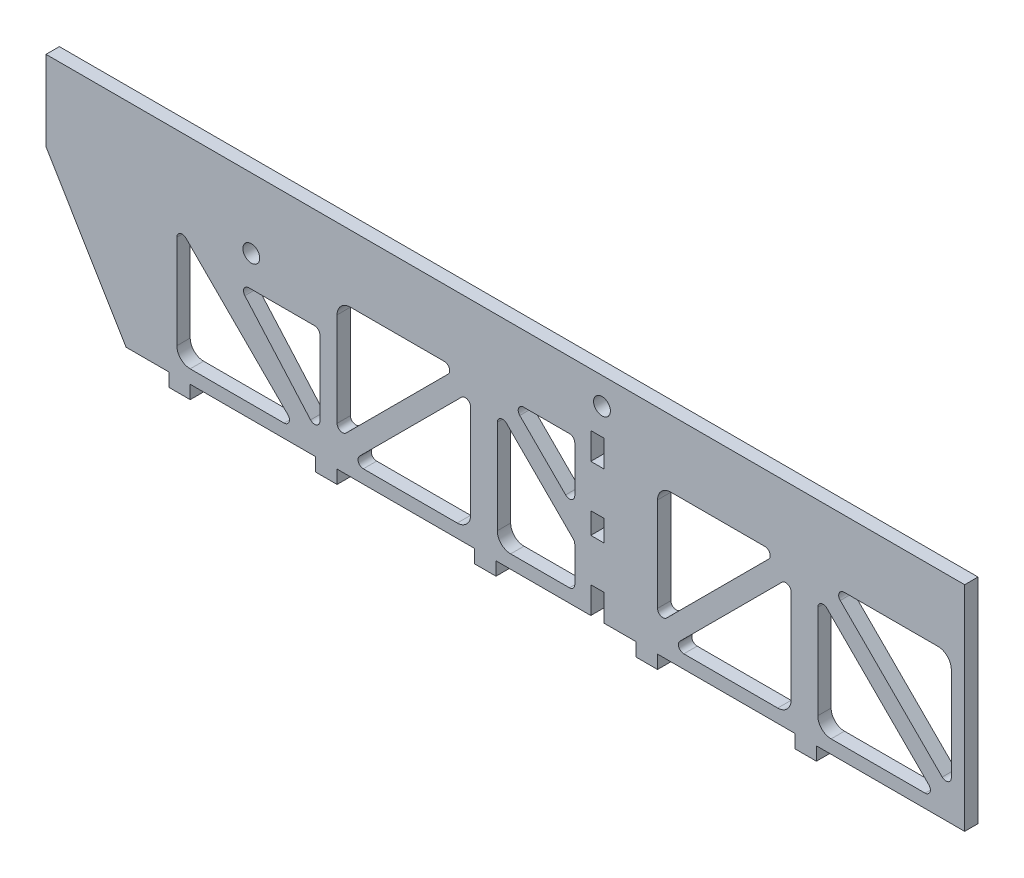
SolidWorks part; units mm, degrees
material "Pine"
ref_plane "Front Plane" through (0, 0, 0) normal (0, 0, 1) x (1, 0, 0)
ref_plane "Top Plane" through (0, 0, 0) normal (0, 1, 0) x (1, 0, 0)
ref_plane "Right Plane" through (0, 0, 0) normal (1, 0, 0) x (0, 0, -1)
sketch "Model" plane through (0, 0, 0) normal (0, 0, 1) x (1, 0, 0)
  line L0 (-306.6281, 15.625) -> (-306.6281, 51.1493)
  line L1 (-309.1681, 53.6893) -> (-340.406, 53.6893)
  line L2 (-342.3135, 49.472) -> (-311.0755, 13.9477)
  line L8 (-171.2321, 6.35) -> (-215.9, 6.35)
  line L9 (-222.25, 57.3679) -> (-222.25, 12.7)
  line L10 (-217.9139, 59.1639) -> (-169.4361, 10.6861)
  line L11 (-234.95, 57.3679) -> (-234.95, 12.7)
  line L12 (-241.3, 6.35) -> (-285.9679, 6.35)
  line L13 (-239.2861, 59.1639) -> (-287.7639, 10.6861)
  line L14 (-294.1139, 17.0361) -> (-245.6361, 65.5139)
  line L15 (-298.45, 63.5) -> (-298.45, 18.8321)
  line L16 (-247.4321, 69.85) -> (-292.1, 69.85)
  line L17 (-323.6321, 6.35) -> (-368.3, 6.35)
  line L18 (-374.65, 57.3679) -> (-374.65, 12.7)
  line L19 (-370.3139, 59.1639) -> (-321.8361, 10.6861)
  line L20 (-18.8321, 6.35) -> (-63.5, 6.35)
  line L21 (-69.85, 57.3679) -> (-69.85, 12.7)
  line L22 (-17.0361, 10.6861) -> (-65.5139, 59.1639)
  line L23 (-82.55, 57.3679) -> (-82.55, 12.7)
  line L24 (-88.9, 6.35) -> (-133.5679, 6.35)
  line L25 (-86.8861, 59.1639) -> (-135.3639, 10.6861)
  line L26 (-93.2361, 65.5139) -> (-141.7139, 17.0361)
  line L27 (-146.05, 63.5) -> (-146.05, 18.8321)
  line L28 (-95.0321, 69.85) -> (-139.7, 69.85)
  line L29 (-163.0861, 17.0361) -> (-211.5639, 65.5139)
  line L30 (-165.1, 69.85) -> (-209.7679, 69.85)
  line L31 (-158.75, 63.5) -> (-158.75, 18.8321)
  line L35 (-398.78, 0) -> (-436.88, 63.5)
  line L36 (0, 0) -> (-398.78, 0)
  line L37 (0, 0) -> (0, 95.25)
  line L38 (0, 95.25) -> (-436.88, 95.25)
  line L39 (-436.88, 63.5) -> (-436.88, 95.25)
  line L40 (-6.35, 63.5) -> (-6.35, 18.8321)
  line L41 (-59.1639, 65.5139) -> (-10.6861, 17.0361)
  line L42 (-12.7, 69.85) -> (-57.3679, 69.85)
  arc A0 (-222.25, 12.7) -> (-215.9, 6.35) centre (-215.9, 12.7) ccw
  arc A1 (-217.9139, 59.1639) -> (-222.25, 57.3679) centre (-219.71, 57.3679) ccw
  arc A2 (-171.2321, 6.35) -> (-169.4361, 10.6861) centre (-171.2321, 8.89) ccw
  arc A3 (-234.95, 57.3679) -> (-239.2861, 59.1639) centre (-237.49, 57.3679) ccw
  arc A4 (-241.3, 6.35) -> (-234.95, 12.7) centre (-241.3, 12.7) ccw
  arc A5 (-287.7639, 10.6861) -> (-285.9679, 6.35) centre (-285.9679, 8.89) ccw
  arc A6 (-245.6361, 65.5139) -> (-247.4321, 69.85) centre (-247.4321, 67.31) ccw
  arc A7 (-298.45, 18.8321) -> (-294.1139, 17.0361) centre (-295.91, 18.8321) ccw
  arc A8 (-292.1, 69.85) -> (-298.45, 63.5) centre (-292.1, 63.5) ccw
  arc A9 (-323.6321, 6.35) -> (-321.8361, 10.6861) centre (-323.6321, 8.89) ccw
  arc A10 (-374.65, 12.7) -> (-368.3, 6.35) centre (-368.3, 12.7) ccw
  arc A11 (-370.3139, 59.1639) -> (-374.65, 57.3679) centre (-372.11, 57.3679) ccw
  arc A12 (-69.85, 12.7) -> (-63.5, 6.35) centre (-63.5, 12.7) ccw
  arc A13 (-65.5139, 59.1639) -> (-69.85, 57.3679) centre (-67.31, 57.3679) ccw
  arc A14 (-18.8321, 6.35) -> (-17.0361, 10.6861) centre (-18.8321, 8.89) ccw
  arc A15 (-82.55, 57.3679) -> (-86.8861, 59.1639) centre (-85.09, 57.3679) ccw
  arc A16 (-88.9, 6.35) -> (-82.55, 12.7) centre (-88.9, 12.7) ccw
  arc A17 (-135.3639, 10.6861) -> (-133.5679, 6.35) centre (-133.5679, 8.89) ccw
  arc A18 (-93.2361, 65.5139) -> (-95.0321, 69.85) centre (-95.0321, 67.31) ccw
  arc A19 (-146.05, 18.8321) -> (-141.7139, 17.0361) centre (-143.51, 18.8321) ccw
  arc A20 (-139.7, 69.85) -> (-146.05, 63.5) centre (-139.7, 63.5) ccw
  arc A21 (-163.0861, 17.0361) -> (-158.75, 18.8321) centre (-161.29, 18.8321) ccw
  arc A22 (-209.7679, 69.85) -> (-211.5639, 65.5139) centre (-209.7679, 67.31) ccw
  arc A23 (-158.75, 63.5) -> (-165.1, 69.85) centre (-165.1, 63.5) ccw
  arc A24 (-306.6281, 15.625) -> (-311.0755, 13.9477) centre (-309.1681, 15.625) cw
  arc A25 (-340.406, 53.6893) -> (-342.3135, 49.472) centre (-340.406, 51.1493) ccw
  arc A26 (-306.6281, 51.1493) -> (-309.1681, 53.6893) centre (-309.1681, 51.1493) ccw
  arc A27 (-10.6861, 17.0361) -> (-6.35, 18.8321) centre (-8.89, 18.8321) ccw
  arc A28 (-57.3679, 69.85) -> (-59.1639, 65.5139) centre (-57.3679, 67.31) ccw
  arc A29 (-6.35, 63.5) -> (-12.7, 69.85) centre (-12.7, 63.5) ccw
  circle A30 centre (-172.466, 88.9) radius 4
  circle A31 centre (-339.2348, 68.4233) radius 4
  dimension "D2" = 172.466
  dimension "D4" = 8
  dimension "D5" = 166.7688
  dimension "D7" = 8
  dimension "D6" = 20.4767
  dimension "D8" = 2.54
  dimension "D1" = 95.25
  dimension "D3" = 6.35
extrude "Boss-Extrude1" add sketch "Model" along normal blind 6.35
sketch "Sketch1" plane through (0, 0, 6.35) normal (0, 0, 1) x (1, 0, 0)
  line L0 (-69.85, 57.3679) -> (-69.85, 12.7) construction
  line L2 (-398.78, 0) -> (0, 0) construction
  line L3 (-146.05, 95.25) -> (-146.05, 0) construction
  line L4 (-146.05, 63.5) -> (-146.05, 18.8321) construction
  line L7 (-298.45, 95.25) -> (-298.45, 0) construction
  line L8 (-298.45, 63.5) -> (-298.45, 18.8321) construction
  line L9 (-222.25, 57.3679) -> (-222.25, 12.7) construction
  line L11 (0, 95.25) -> (-436.88, 95.25) construction
  line L12 (-70.485, 0) -> (-80.645, 0)
  line L13 (-70.485, 0) -> (-70.485, -6.35)
  line L14 (-70.485, -6.35) -> (-80.645, -6.35)
  line L15 (-80.645, 0) -> (-80.645, -6.35)
  line L16 (-146.05, 0) -> (-156.21, 0)
  line L17 (-146.05, 0) -> (-146.05, -6.35)
  line L18 (-146.05, -6.35) -> (-156.21, -6.35)
  line L19 (-156.21, 0) -> (-156.21, -6.35)
  line L20 (-222.885, 0) -> (-233.045, 0)
  line L21 (-222.885, 0) -> (-222.885, -6.35)
  line L22 (-222.885, -6.35) -> (-233.045, -6.35)
  line L23 (-233.045, 0) -> (-233.045, -6.35)
  line L24 (-298.45, 0) -> (-308.61, 0)
  line L25 (-298.45, 0) -> (-298.45, -6.35)
  line L26 (-298.45, -6.35) -> (-308.61, -6.35)
  line L27 (-308.61, 0) -> (-308.61, -6.35)
  line L28 (-368.3, 0) -> (-378.46, 0)
  line L29 (-368.3, 0) -> (-368.3, -6.35)
  line L30 (-368.3, -6.35) -> (-378.46, -6.35)
  line L31 (-378.46, 0) -> (-378.46, -6.35)
  line L32 (0, 0) -> (0, 95.25) construction
  line L53 (-436.88, 95.25) -> (0, 95.25)
  line L54 (-436.88, 95.25) -> (-436.88, 101.6)
  line L55 (-436.88, 101.6) -> (0, 101.6)
  line L56 (0, 95.25) -> (0, 101.6)
  dimension "D1" = 6.35
  dimension "D2" = 10.16
  dimension "D3" = 10.16
  dimension "D4" = 10.16
  dimension "D5" = 10.16
  dimension "D6" = 10.16
  dimension "D7" = 20.32
  dimension "D8" = 6.35
  dimension "D9" = 0.635
  dimension "D10" = 0.635
extrude "Boss-Extrude2" add sketch "Sketch1" against normal up to surface (6.35 mm away) up to face at (-168.466, 88.9, 0)
sketch "Sketch2" plane through (0, 0, 0) normal (0, 0, -1) x (-1, 0, 0)
  line L0 (158.75, 18.8321) -> (158.75, 63.5) construction
  line L1 (185.42, 69.85) -> (165.1, 69.85)
  line L2 (185.42, 69.85) -> (185.42, 0)
  line L3 (185.42, 0) -> (165.1, 0)
  line L4 (165.1, 69.85) -> (165.1, 0)
  line L6 (222.885, 0) -> (156.21, 0) construction
  line L8 (165.1, 69.85) -> (209.7679, 69.85) construction
  line L10 (156.21, -6.35) -> (146.05, -6.35) construction
  line L11 (177.8, 0) -> (171.45, 0)
  line L12 (177.8, 0) -> (177.8, 12.7)
  line L13 (177.8, 12.7) -> (171.45, 12.7)
  line L14 (171.45, 0) -> (171.45, 12.7)
  line L15 (177.8, 33.02) -> (171.45, 33.02)
  line L16 (177.8, 33.02) -> (177.8, 43.18)
  line L17 (177.8, 43.18) -> (171.45, 43.18)
  line L18 (171.45, 33.02) -> (171.45, 43.18)
  line L19 (177.8, 63.5) -> (171.45, 63.5)
  line L20 (177.8, 63.5) -> (177.8, 76.2)
  line L21 (177.8, 76.2) -> (171.45, 76.2)
  line L22 (171.45, 63.5) -> (171.45, 76.2)
  dimension "D1" = 6.35
  dimension "D2" = 20.32
  dimension "D3" = 10.16
  dimension "D4" = 12.7
  dimension "D5" = 6.35
  dimension "D6" = 20.32
  dimension "D7" = 20.32
  dimension "D8" = 12.7
  dimension "D9" = 6.35
  dimension "D10" = 6.35
extrude "Boss-Extrude3" add sketch "Sketch2" against normal up to surface (6.35 mm away) contours L4 | L19 L22 L1 L4 L3 L14 L13 L12 L2 L20 L15 L18 L17 L16 region at (-184.6925, 34.925, 0) up to face at (-319.4123, 39.5294, 6.35)
extrude "Cut-Extrude1" cut sketch "Sketch2<3>" against normal blind 6.35 contours L22 L1 L20 L21 | L14 L3 L12 L13 region at (-174.625, 73.025, 0) region at (-174.625, 6.35, 0)
sketch "Sketch2<3>" plane through (0, 0, 0) normal (0, 0, -1) x (-1, 0, 0) same geometry as "Sketch2"
sketch "Sketch3" plane through (0, 0, 0) normal (0, 0, -1) x (-1, 0, 0)
  line L1 (154.4024, 72.7027) -> (167.3891, 72.7027)
  line L2 (154.4024, 72.7027) -> (154.4024, 13.591)
  line L3 (154.4024, 13.591) -> (167.3891, 13.591)
  line L4 (167.3891, 72.7027) -> (167.3891, 13.591)
extrude "Boss-Extrude4" add sketch "Sketch3" against normal up to surface (6.35 mm away) up to face at (-224.0455, 7.8828, 6.35)
sketch "Sketch4" plane through (0, 0, 6.35) normal (0, 0, 1) x (1, 0, 0)
  line L0 (-185.42, 69.85) -> (-209.7679, 69.85) construction
  line L1 (-185.42, 39.37) -> (-185.42, 69.85) construction
  line L2 (-211.5639, 65.5139) -> (-185.42, 39.37) construction
  line L3 (-185.42, 26.67) -> (-217.9139, 59.1639) construction
  line L4 (-185.42, 6.35) -> (-185.42, 26.67) construction
  line L5 (-215.9, 6.35) -> (-185.42, 6.35) construction
  line L6 (-187.96, 69.85) -> (-209.7679, 69.85)
  line L7 (-185.42, 45.5021) -> (-185.42, 67.31)
  line L8 (-211.5639, 65.5139) -> (-189.7561, 43.7061)
  line L9 (-186.1639, 27.4139) -> (-217.9139, 59.1639)
  line L10 (-185.42, 8.89) -> (-185.42, 25.6179)
  line L11 (-215.9, 6.35) -> (-187.96, 6.35)
  line L12 (-187.96, 6.35) -> (-185.42, 6.35)
  line L13 (-185.42, 6.35) -> (-185.42, 8.89)
  line L14 (-185.42, 25.6179) -> (-185.42, 26.67)
  line L15 (-185.42, 26.67) -> (-186.1639, 27.4139)
  line L16 (-185.42, 45.5021) -> (-185.42, 39.37)
  line L17 (-185.42, 39.37) -> (-189.7561, 43.7061)
  line L18 (-187.96, 69.85) -> (-185.42, 69.85)
  line L19 (-185.42, 69.85) -> (-185.42, 67.31)
  arc A0 (-187.96, 69.85) -> (-185.42, 67.31) centre (-187.96, 67.31) cw
  arc A1 (-185.42, 45.5021) -> (-189.7561, 43.7061) centre (-187.96, 45.5021) cw
  arc A2 (-186.1639, 27.4139) -> (-185.42, 25.6179) centre (-187.96, 25.6179) cw
  arc A3 (-187.96, 6.35) -> (-185.42, 8.89) centre (-187.96, 8.89) ccw
  dimension "D1" = 2.54
extrude "Boss-Extrude6" add sketch "Sketch4" against normal up to surface (6.35 mm away) contours A3 L12 L13 | L15 A2 L14 | L16 A1 L17 | L18 A0 L19 region at (-185.9874, 69.2826, 6.35) region at (-186.5486, 42.0946, 6.35) region at (-185.5728, 26.6067, 6.35) region at (-185.9874, 6.9174, 6.35) up to face at (-208.5115, 28.1226, 0)
equation "\"thick\"=0.25"
equation "\"D1@Boss-Extrude1\"=\"thick\""
